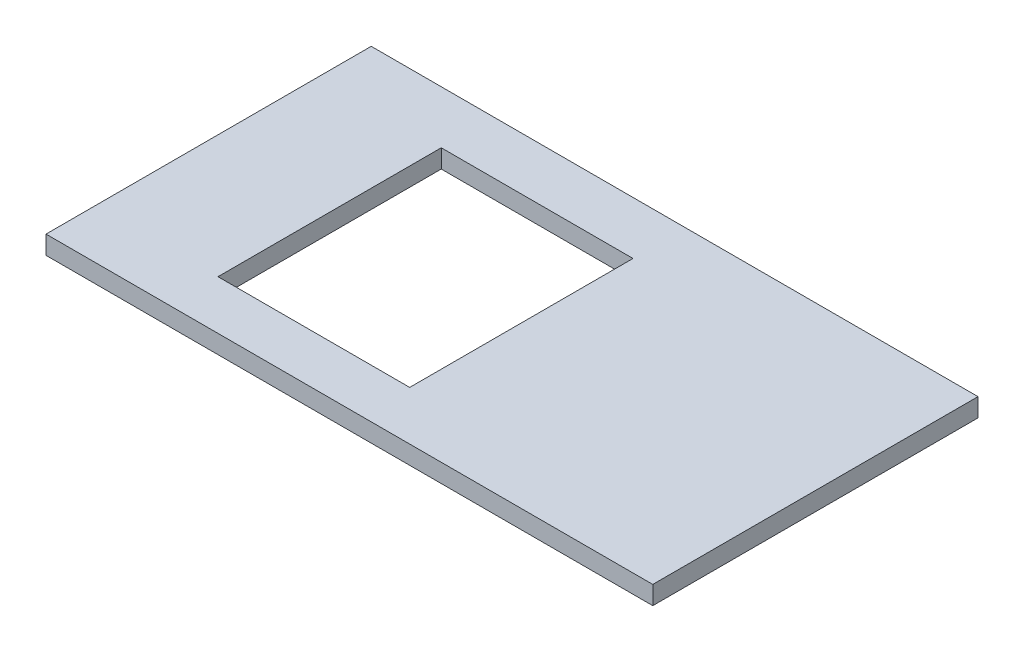
SolidWorks part; units mm, degrees
ref_plane "Спереди" through (0, 0, 0) normal (0, 0, 1) x (1, 0, 0)
ref_plane "Сверху" through (0, 0, 0) normal (0, 1, 0) x (1, 0, 0)
ref_plane "Справа" through (0, 0, 0) normal (1, 0, 0) x (0, 0, -1)
sketch "Эскиз1" plane through (0, 0, 0) normal (0, 1, 0) x (1, 0, 0)
  line L0 (0, 0) -> (0, 670)
  line L1 (0, 670) -> (1250, 670)
  line L2 (1250, 670) -> (1250, 0)
  line L5 (1250, 0) -> (0, 0)
  point P3 (1630, -930)
  point P6 (1642.9342, 0)
  point P7 (0, 0)
  point P8 (1630, 0)
  dimension "D1" = 670
  dimension "D2" = 1250
extrude "Бобышка-Вытянуть1" add sketch "Эскиз1" along normal blind 38
sketch "Эскиз2" plane through (0, 38, 0) normal (0, 1, 0) x (1, 0, 0)
  line L1 (253.1553, 561.1164) -> (648.1553, 561.1164)
  line L2 (253.1553, 561.1164) -> (253.1553, 101.1164)
  line L3 (253.1553, 101.1164) -> (648.1553, 101.1164)
  line L4 (648.1553, 561.1164) -> (648.1553, 101.1164)
extrude "Вырез-Вытянуть1" cut sketch "Эскиз2" against normal through all
